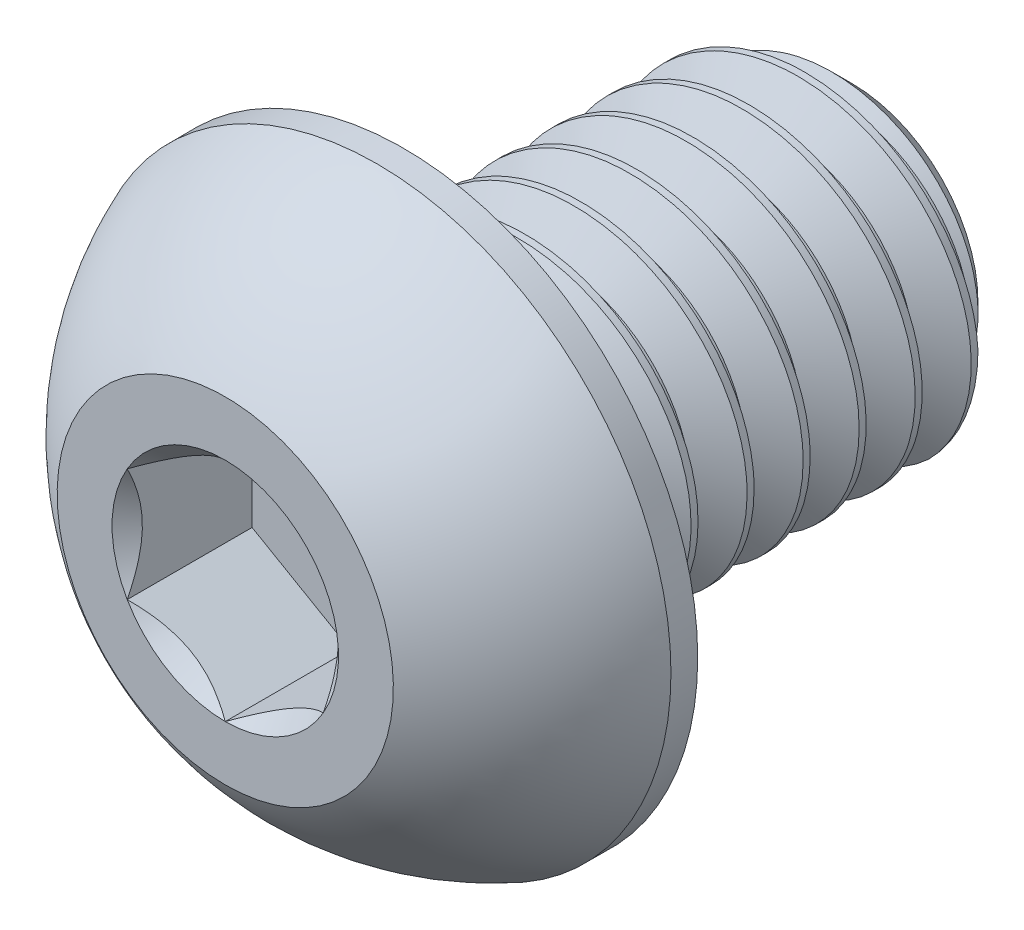
SolidWorks part; units mm, degrees
ref_plane "Front" through (0, 0, 0) normal (0, 0, 1) x (1, 0, 0)
ref_plane "Top" through (0, 0, 0) normal (0, 1, 0) x (1, 0, 0)
ref_plane "Right" through (0, 0, 0) normal (1, 0, 0) x (0, 0, -1)
sketch "Sketch1" plane through (0, 0, 0) normal (1, 0, 0) x (0, 0, -1)
  line L2 (5.0546, 4.7625) -> (17.7546, 4.7625)
  line L3 (17.7546, 4.7625) -> (17.7546, 0)
  line L4 (17.7546, 0) -> (5.0546, 0)
  line L6 (4.2964, 8.3312) -> (5.0546, 8.3312) construction
  line L7 (17.7546, 4.7625) -> (17.7546, -4.7625) construction
  line L8 (0, 0) -> (5.0546, 0) construction
  line L9 (5.0546, 8.3312) -> (5.0546, -8.3312) construction
  line L11 (5.0546, 4.7625) -> (5.0546, 0)
  line L13 (0, 2.7781) -> (0, -2.7781) construction
  line L14 (0, 2.7781) -> (0, 4.7625) construction
  arc A3 (0, 4.7625) -> (4.2964, 8.3312) centre (7.5862, 0) cw construction
  dimension "D1" = 0.7582
revolve "Revolve1" add sketch "Sketch1" angle 360 mid plane about L4
sketch "Sketch3" plane through (0, 0, -17.7546) normal (0, 0, -1) x (-1, 0, 0)
  circle A0 centre (0, 0) radius 4.7625
curve "Helix/Spiral1" pitch 1.5875 height 14.2875 radius 4.7625 centre (0, 0, -17.7546) axis (0, 0, 1) start towards (0, 1, 0)
sketch "Sketch2" plane through (0, 0, 0) normal (1, 0, 0) x (0, 0, -1)
  line L0 (17.7546, 4.7625) -> (19.1437, 4.7625)
  line L1 (19.1437, 4.7625) -> (18.5484, 3.7314)
  line L2 (18.5484, 3.7314) -> (18.3499, 3.7314)
  line L3 (18.3499, 3.7314) -> (17.7546, 4.7625)
  line L4 (18.0523, 4.2469) -> (18.846, 4.2469) construction
  dimension "D1" = 60
  dimension "D2" = 0.1984
  dimension "D3" = 0.7937
chamfer "Chamfer1" distance 1.1906 angle 45 1 edges at (0, 4.7625, -17.7546)
sweep "Cut-Sweep1" cut profiles "Sketch2" path "Helix/Spiral1" align with end faces yes
sketch "Sketch7" plane through (0, 0, 0) normal (1, 0, 0) x (0, 0, -1)
  line L6 (4.2964, 8.3312) -> (5.0546, 8.3312) construction
  line L8 (0, 0) -> (5.0546, 0) construction
  line L11 (5.0546, 8.3312) -> (5.0546, -8.3312) construction
  line L12 (4.2964, 8.3312) -> (5.0546, 8.3312)
  line L13 (0, 0) -> (5.0546, 0)
  line L14 (0, 2.7781) -> (0, -2.7781) construction
  line L15 (5.0546, 8.3312) -> (5.0546, 0)
  line L16 (0, 4.7625) -> (0, 0)
  arc A2 (4.2964, 8.3312) -> (0, 4.7625) centre (7.5862, 0) ccw construction
  arc A3 (4.2964, 8.3312) -> (0, 4.7625) centre (7.5862, 0) ccw
revolve "Revolve2" add sketch "Sketch7" angle 360 mid plane about L13
sketch "Sketch5" plane through (0, 0, 0) normal (0, 0, 1) x (1, 0, 0)
  line L1 (2.7781, -1.604) -> (2.7781, 1.604)
  line L2 (2.7781, 1.604) -> (0, 3.2079)
  line L3 (0, 3.2079) -> (-2.7781, 1.604)
  line L4 (-2.7781, 1.604) -> (-2.7781, -1.604)
  line L5 (-2.7781, -1.604) -> (0, -3.2079)
  line L6 (0, -3.2079) -> (2.7781, -1.604)
  circle A0 centre (0, 0) radius 2.7781 construction
extrude "Cut-Extrude2" cut sketch "Sketch5" against normal blind 3.5382
sketch "Sketch6" plane through (0, 0, 0) normal (0, 0, 1) x (1, 0, 0)
  circle A0 centre (0, 0) radius 3.2079
extrude "Cut-Extrude3" cut sketch "Sketch6" against normal blind 3.5382 draft 45
sketch "Sketch9" [suppressed] plane through (0, 0, -5.0546) normal (0, 0, 1) x (1, 0, 0)
  circle A2 centre (0, 0) radius 4.7625
extrude "Boss-Extrude2" [suppressed] add sketch "Sketch9" against normal offset from surface (19.05 mm away) 28.575 up to face at (0, 3.5719, -17.7546)
sketch "Sketch10" plane through (0, 0, 0) normal (1, 0, 0) x (0, 0, -1)
  line L0 (17.7546, 4.7625) -> (17.7546, -4.7625) construction
  point P0 (15.3734, -4.7625)
  dimension "D1" = 2.3813
equation "\"D3@Helix/Spiral1\" = \"Lg@Sketch1\" + \"D4@Helix/Spiral1\""
equation "\"D2@Sketch2\" = \"D4@Helix/Spiral1\" * .125"
equation "\"D3@Sketch2\" = \"D4@Helix/Spiral1\" * .5"
equation "\"D1@Chamfer1\" = \"D4@Helix/Spiral1\" * .75"
equation "\"D1@Cut-Extrude2\" = \"Head Ht@Sketch1\" * .7"
equation "\"D1@Sketch1\" = \"Head Ht@Sketch1\" * .15"
equation "\"D1@Sketch10\" = \"D4@Helix/Spiral1\" * 1.5"
equation "\"D1@Cut-Extrude3\" = \"D1@Cut-Extrude2\""
